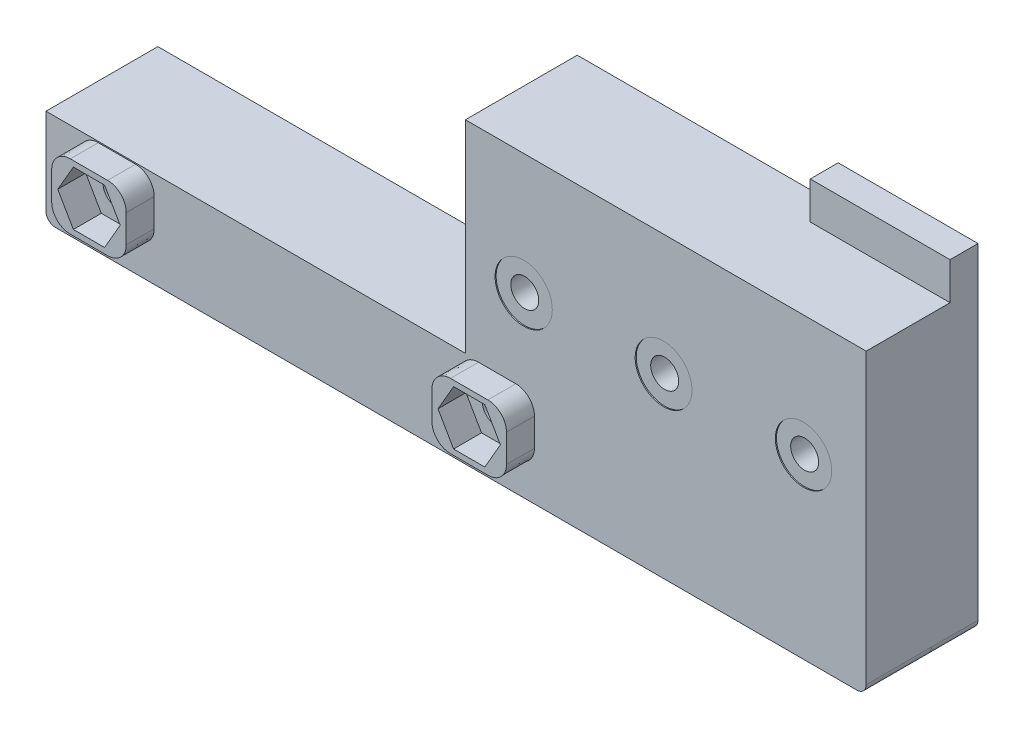
SolidWorks part; units mm, degrees
note: The reader was unsure of these and kept them because the rebuilt part matched: shared geometry of "Sketch3<6>", "Sketch3<9>", "Sketch3<11>", "Sketch3<14>", "Sketch3<15>".
ref_plane "Front Plane" through (0, 0, 0) normal (0, 0, 1) x (1, 0, 0)
ref_plane "Top Plane" through (0, 0, 0) normal (0, 1, 0) x (1, 0, 0)
ref_plane "Right Plane" through (0, 0, 0) normal (1, 0, 0) x (0, 0, -1)
other "Graphic1"
other "Graphic (Closed) -1"
other "Graphic (Closed) -2"
other "Graphic (Open) -1"
ref_plane "Plane1" through (0, 0, -78.8879) normal (0, 0, 1) x (1, 0, 0)
sketch "Sketch2" plane through (0, 0, -78.8879) normal (0, 0, 1) x (1, 0, 0)
  line L0 (284.7238, -118.3113) -> (241.7238, -118.3114)
  line L1 (241.7238, -118.3114) -> (241.7238, -135.5153)
  line L2 (241.7238, -135.5153) -> (196.7238, -135.5153)
  line L5 (284.7238, -118.3113) -> (284.7238, -145.8113)
  line L7 (196.7238, -135.5153) -> (196.7238, -145.8113)
  line L8 (284.7238, -145.8113) -> (196.7238, -145.8113)
  circle A0 centre (278.0059, -126.7978) radius 1.5
  circle A1 centre (262.988, -126.7978) radius 1.5
  circle A2 centre (247.9759, -126.7978) radius 1.5
  circle A3 centre (245.0379, -139.1031) radius 1.5
  circle A4 centre (204.3453, -139.1851) radius 1.5
  dimension "D6" = 3
  dimension "D7" = 3
  dimension "D8" = 3
  dimension "D9" = 3
  dimension "D10" = 3
  dimension "D1" = 27.5
  dimension "D2" = 43
  dimension "D3" = 45
  dimension "D4" = 88
  dimension "D5" = 10.2961
sketch "Sketch3" plane through (0, 0, -78.8879) normal (0, 0, 1) x (1, 0, 0)
  line L0 (248.48, -139.1403) -> (246.8057, -136.2403)
  line L1 (246.8057, -136.2403) -> (243.457, -136.2403)
  line L2 (243.457, -136.2403) -> (241.7827, -139.1403)
  line L3 (241.7827, -139.1403) -> (243.457, -142.0403)
  line L4 (243.457, -142.0403) -> (246.8057, -142.0403)
  line L5 (246.8057, -142.0403) -> (248.48, -139.1403)
  line L6 (247.1314, -135.6403) -> (243.1314, -135.6403)
  line L7 (241.1459, -137.3992) -> (241.1314, -140.6403)
  line L8 (242.6527, -142.5821) -> (242.8903, -142.6257)
  line L9 (242.8903, -142.6257) -> (243.1314, -142.6403)
  line L10 (243.1314, -142.6403) -> (247.1314, -142.6403)
  line L11 (249.1314, -140.6403) -> (249.1314, -137.6403)
  line L12 (206.0081, -136.2388) -> (202.6594, -136.2388)
  line L13 (202.6594, -136.2388) -> (200.9851, -139.1388)
  line L14 (200.9851, -139.1388) -> (202.6594, -142.0388)
  line L15 (202.6594, -142.0388) -> (206.0081, -142.0388)
  line L16 (206.0081, -142.0388) -> (207.6824, -139.1388)
  line L17 (207.6824, -139.1388) -> (206.0081, -136.2388)
  line L18 (206.3337, -135.6388) -> (202.3337, -135.6388)
  line L19 (200.3337, -137.6388) -> (200.3337, -140.6388)
  line L20 (202.3337, -142.6388) -> (206.3337, -142.6388)
  line L21 (208.3337, -137.6388) -> (208.3337, -140.6388)
  line L22 (196.7238, -135.5153) -> (196.7238, -145.8113)
  line L23 (196.7238, -145.8113) -> (284.7238, -145.8113)
  line L24 (284.7238, -145.8113) -> (284.7238, -118.3113)
  line L25 (284.7238, -118.3113) -> (241.7238, -118.3114)
  line L26 (241.7238, -118.3114) -> (241.7238, -135.5153)
  line L27 (241.7238, -135.5153) -> (196.7238, -135.5153)
  circle A0 centre (247.9759, -126.7978) radius 3.0715
  circle A1 centre (262.988, -126.7978) radius 3.0491
  circle A2 centre (278.0059, -126.7978) radius 3.0268
  circle A3 centre (278.0059, -126.7978) radius 3.0268
  circle A4 centre (278.0059, -126.7978) radius 1.5
  circle A5 centre (262.988, -126.7978) radius 1.5
  circle A6 centre (247.9759, -126.7978) radius 1.5
  circle A7 centre (245.0379, -139.1031) radius 1.5
  circle A8 centre (204.3453, -139.1851) radius 1.5
  spline S0 degree 3 poles (249.1314, -137.6403) (249.1314, -137.4791) (249.102, -137.2375) (249.0059, -136.9293) (248.9066, -136.7086) (248.7813, -136.5014) (248.632, -136.3108) (248.4608, -136.1396) (248.2703, -135.9903) (248.0631, -135.865) (247.8423, -135.7657) (247.5341, -135.6696) (247.2925, -135.6402) (247.1314, -135.6403) knots 0 0 0 0 0.153848 0.230771 0.307692 0.384614 0.461538 0.538462 0.615386 0.692308 0.769229 0.846156 1 1 1 1
  spline S1 degree 3 poles (243.1314, -135.6403) (242.9702, -135.6402) (242.7286, -135.6696) (242.4204, -135.7657) (242.1996, -135.865) (241.9925, -135.9903) (241.8019, -136.1396) (241.6307, -136.3108) (241.4814, -136.5014) (241.3561, -136.7085) (241.2236, -137.0029) (241.1653, -137.2392) (241.1459, -137.3992) knots 0 0 0 0 0.166669 0.250001 0.333338 0.416665 0.499999 0.583333 0.666667 0.750001 0.833333 1 1 1 1
  spline S2 degree 3 poles (241.1314, -140.6403) (241.1313, -140.8014) (241.1607, -141.043) (241.2568, -141.3512) (241.3561, -141.572) (241.4814, -141.7792) (241.6307, -141.9697) (241.8019, -142.1409) (241.9925, -142.2902) (242.2687, -142.4573) (242.4963, -142.5436) (242.6527, -142.5821) knots 0 0 0 0 0.18182 0.272729 0.363636 0.454551 0.545457 0.636366 0.727276 0.818186 1 1 1 1
  spline S3 degree 3 poles (247.1314, -142.6403) (247.2925, -142.6403) (247.5341, -142.6109) (247.8423, -142.5148) (248.0631, -142.4155) (248.2703, -142.2902) (248.5241, -142.0915) (248.7399, -141.8479) (248.9066, -141.572) (249.006, -141.3512) (249.102, -141.043) (249.1314, -140.8014) (249.1314, -140.6403) knots 0 0 0 0 0.153887 0.230836 0.307779 0.384722 0.461668 0.615278 0.692221 0.769164 0.846108 1 1 1 1
  spline S4 degree 3 poles (208.3337, -137.6388) (208.3338, -137.4777) (208.3044, -137.236) (208.2083, -136.9278) (208.109, -136.7071) (207.9837, -136.4999) (207.8344, -136.3093) (207.6632, -136.1381) (207.4726, -135.9888) (207.2654, -135.8635) (207.0447, -135.7642) (206.7365, -135.6681) (206.4948, -135.6387) (206.3337, -135.6388) knots 0 0 0 0 0.153844 0.230771 0.307693 0.384614 0.461542 0.538465 0.615386 0.692308 0.769233 0.846156 1 1 1 1
  spline S5 degree 3 poles (202.3337, -135.6388) (202.1726, -135.6387) (201.931, -135.6681) (201.6228, -135.7642) (201.402, -135.8635) (201.1948, -135.9888) (201.0043, -136.1381) (200.8331, -136.3093) (200.6838, -136.4999) (200.5585, -136.7071) (200.4591, -136.9278) (200.3631, -137.236) (200.3337, -137.4777) (200.3337, -137.6388) knots 0 0 0 0 0.153848 0.230771 0.307696 0.384618 0.461541 0.538464 0.615385 0.692309 0.769234 0.846157 1 1 1 1
  spline S6 degree 3 poles (200.3337, -140.6388) (200.3337, -140.7999) (200.3631, -141.0415) (200.4591, -141.3497) (200.5585, -141.5705) (200.6838, -141.7777) (200.8331, -141.9682) (201.0043, -142.1394) (201.1948, -142.2887) (201.402, -142.414) (201.6228, -142.5134) (201.931, -142.6094) (202.1726, -142.6388) (202.3337, -142.6388) knots 0 0 0 0 0.153847 0.230769 0.30769 0.384618 0.461538 0.538461 0.615381 0.692305 0.769231 0.846153 1 1 1 1
  spline S7 degree 3 poles (206.3337, -142.6388) (206.4949, -142.6388) (206.7365, -142.6094) (207.0447, -142.5134) (207.2654, -142.414) (207.4726, -142.2887) (207.6632, -142.1394) (207.8344, -141.9682) (207.9837, -141.7777) (208.109, -141.5705) (208.2083, -141.3497) (208.3044, -141.0415) (208.3338, -140.7999) (208.3337, -140.6388) knots 0 0 0 0 0.153844 0.230765 0.307691 0.384615 0.461535 0.538458 0.615382 0.692308 0.769229 0.846152 1 1 1 1
extrude "Boss-Extrude4" add sketch "Sketch3" along normal blind 7 contours L26 L27 L22 L23 L24 L25 S7 L20 S6 L19 S5 L18 S4 L21 S3 L10 L9 L8 S2 L7 S1 L6 S0 L11 A2 A1 A0
extrude "Boss-Extrude5" add sketch "Sketch3<6>" along normal blind 10 contours L10 S3 L11 S0 L6 S1 L7 S2 L8 L9 L5 L4 L3 L2 L1 L0 | L20 S7 L21 S4 L18 S5 L19 S6 L17 L16 L15 L14 L13 L12
sketch "Sketch3<6>" plane through (0, 0, -78.8879) normal (0, 0, 1) x (1, 0, 0) same geometry as "Sketch3"
extrude "Boss-Extrude8" add sketch "Sketch3<9>" along normal blind 7 contours L4 L5 L0 L1 L2 L3 A7
sketch "Sketch3<9>" plane through (0, 0, -78.8879) normal (0, 0, 1) x (1, 0, 0) same geometry as "Sketch3"
fillet "Fillet3" radius 1 2 edges at (284.7238, -145.8113, -75.3879) (196.7238, -145.8113, -75.3879)
extrude "Boss-Extrude10" add sketch "Sketch3<11>" along normal blind 7 contours L16 L17 L12 L13 L14 L15 A8
sketch "Sketch3<11>" plane through (0, 0, -78.8879) normal (0, 0, 1) x (1, 0, 0) same geometry as "Sketch3"
ref_plane "Plane2" through (0, 0, -72.0059) normal (0, 0, 1) x (1, 0, 0)
sketch "Sketch4" plane through (0, 0, -72.0059) normal (0, 0, 1) x (1, 0, 0)
  circle A0 centre (247.9759, -126.7978) radius 3.0715
  circle A2 centre (262.988, -126.7978) radius 3.0491
  circle A3 centre (278.0059, -126.7978) radius 3.0268
  circle A5 centre (247.9759, -126.7978) radius 1.5
  circle A6 centre (262.988, -126.7978) radius 1.5
  circle A7 centre (278.0059, -126.7978) radius 1.5
extrude "Boss-Extrude11" add sketch "Sketch4" against normal blind 3
extrude "Boss-Extrude12" add sketch "Sketch2" against normal blind 5
extrude "Cut-Extrude2" cut sketch "Sketch3<14>" against normal blind 5 contours A2 A4 | A1 A5 | A0 A6
sketch "Sketch3<14>" plane through (0, 0, -78.8879) normal (0, 0, 1) x (1, 0, 0) same geometry as "Sketch3"
extrude "Boss-Extrude13" add sketch "Sketch3<15>" along normal blind 5 contours A2 A4 | A1 A5 | A0 A6
sketch "Sketch3<15>" plane through (0, 0, -78.8879) normal (0, 0, 1) x (1, 0, 0) same geometry as "Sketch3"
fillet "Fillet4" radius 1 2 edges at (196.7238, -145.8113, -81.3879) (284.7238, -145.8113, -81.3879)
ref_plane "Plane3" through (0, -118.3114, 0) normal (0, 1, 0) x (1, 0, 0)
sketch "Sketch5" plane through (0, -118.3114, 0) normal (0, 1, 0) x (1, 0, 0)
  line L0 (241.7237, 83.8879) -> (241.7237, 71.8879)
  line L1 (241.7237, 71.8879) -> (284.7237, 71.8879)
  line L2 (284.7237, 71.8879) -> (284.7237, 83.8879)
  line L3 (284.7237, 83.8879) -> (241.7237, 83.8879)
extrude "Boss-Extrude14" add sketch "Sketch5" along normal blind 4.5
ref_plane "Plane4" through (284.7238, 0, 0) normal (1, 0, 0) x (0, 0, -1)
sketch "Sketch6" plane through (284.7238, 0, 0) normal (1, 0, 0) x (0, 0, -1)
  line L0 (83.8879, -113.8113) -> (80.8879, -113.8113)
  line L1 (71.8879, -113.8113) -> (83.8879, -113.8113) construction
  line L2 (80.8879, -113.8113) -> (80.8879, -109.8113)
  line L3 (80.8879, -109.8113) -> (83.8879, -109.8113)
  line L4 (83.8879, -109.8113) -> (83.8879, -113.8113)
  dimension "D1" = 4
  dimension "D2" = 3
extrude "Boss-Extrude15" add sketch "Sketch6" against normal blind 15
